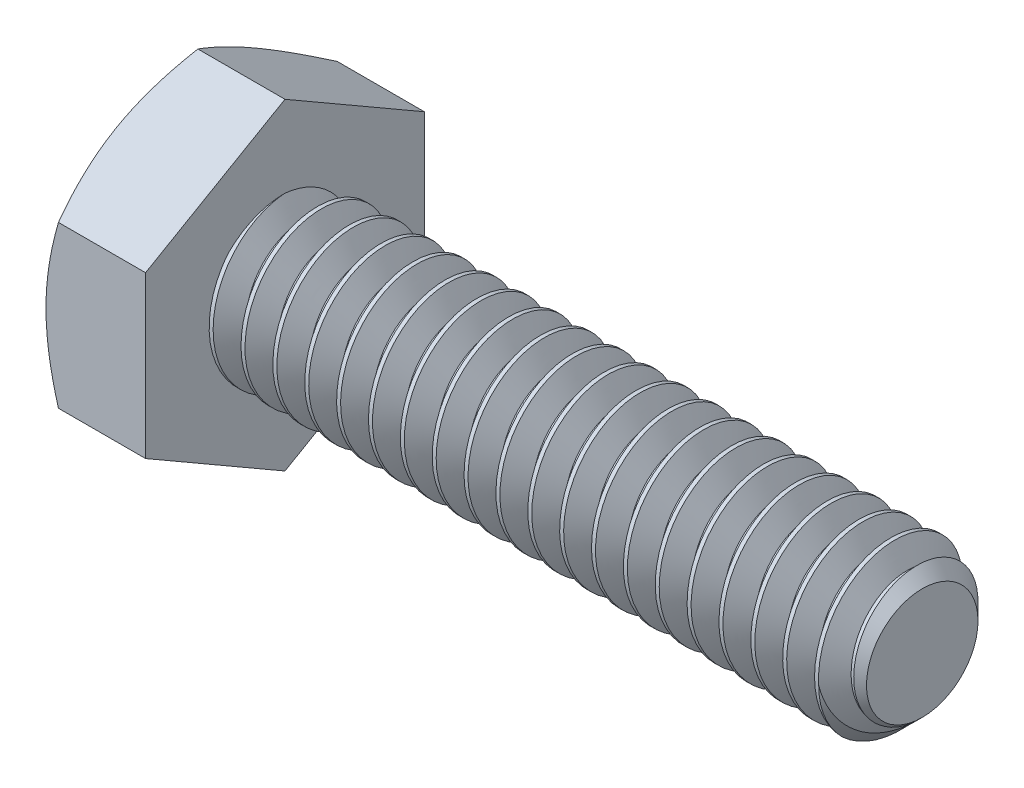
SolidWorks part; units mm, degrees
ref_plane "Front Plane" through (0, 0, 0) normal (0, 0, 1) x (1, 0, 0)
ref_plane "Top Plane" through (0, 0, 0) normal (0, 1, 0) x (1, 0, 0)
ref_plane "Right Plane" through (0, 0, 0) normal (1, 0, 0) x (0, 0, -1)
sketch "Sketch1" plane through (0, 0, 0) normal (0, 0, 1) x (1, 0, 0)
  line L0 (-14.6844, 0) -> (14.6844, 0) construction
  line L1 (14.6844, 3.175) -> (14.6844, -3.175) construction
  line L2 (-10.7156, 5.5562) -> (-10.7156, -5.5562) construction
  line L3 (-14.6844, 5.5562) -> (-14.6844, -5.5562) construction
  point P9 (-10.7156, 0)
  point P10 (10.2394, -3.175)
  dimension "Screw Dia" = 6.35
  dimension "Hex" = 11.1125
  dimension "Head Ht" = 3.9688
  dimension "Screw Lenght" = 25.4
  dimension "D1" = 4.445
ref_plane "Plane2" through (14.6844, 0, 0) normal (1, 0, 0) x (0, 0, -1)
sketch "Sketch5" plane through (14.6844, 0, 0) normal (1, 0, 0) x (0, 0, -1)
  circle A0 centre (0, 0) radius 3.175
extrude "Boss-Extrude3" add sketch "Sketch5" against normal up to vertex (25.4 mm away) up to point (-10.7156, 0, 0)
sketch "Sketch9" plane through (14.6844, 0, 0) normal (1, 0, 0) x (0, 0, -1)
  circle A1 centre (0, 0) radius 3.175
  circle A2 centre (0, 0) radius 3.175
  dimension "D1" = 0
curve "Helix/Spiral1" pitch 1.27 height 26.67 turns 21 parameters "Pitch"=1.27
chamfer "Chamfer1" distance 0.9525 angle 45 1 edges at (14.6844, 0, -3.175)
sketch "Sketch10" plane through (0, 0, 0) normal (0, 0, 1) x (1, 0, 0)
  line L0 (14.6844, 3.175) -> (15.1606, 2.3501)
  line L1 (15.1606, 2.3501) -> (15.3194, 2.3501)
  line L2 (15.3194, 2.3501) -> (15.7956, 3.175)
  line L3 (14.6844, 3.175) -> (15.7956, 3.175)
  line L4 (15.24, 3.175) -> (15.24, 2.3501) construction
  line L5 (14.9225, 2.7626) -> (15.5575, 2.7626) construction
  dimension "D1" = 60
  dimension "D2" = 0.1588
  dimension "D3" = 0.635
sweep "Cut-Sweep1" cut profiles "Sketch10" path "Helix/Spiral1" align with end faces yes
sketch "Sketch6" plane through (-10.7156, 0, 0) normal (-1, 0, 0) x (0, 0, 1)
  line L0 (0, 5.5562) -> (0, -5.5562) construction
  line L1 (5.5562, 3.2079) -> (0, 6.4158)
  line L2 (0, 6.4158) -> (-5.5562, 3.2079)
  line L3 (-5.5562, 3.2079) -> (-5.5562, -3.2079)
  line L4 (-5.5562, -3.2079) -> (0, -6.4158)
  line L5 (0, -6.4158) -> (5.5563, -3.2079)
  line L6 (5.5563, -3.2079) -> (5.5562, 3.2079)
  circle A0 centre (0, 0) radius 5.5562 construction
extrude "Boss-Extrude4" add sketch "Sketch6" along normal up to vertex (3.9688 mm away) up to point (-14.6844, -5.5562, 0)
sketch "Sketch7" plane through (-14.6844, 0, 0) normal (-1, 0, 0) x (0, 0, 1)
  circle A0 centre (0, 0) radius 5.5562 construction
  circle A1 centre (0, 0) radius 5.5562
sketch "Sketch8" plane through (-14.6844, 0, 0) normal (-1, 0, 0) x (0, 0, 1)
  circle A0 centre (0, 0) radius 5.5562 construction
  circle A1 centre (0, 0) radius 5.5562
extrude "Cut-Extrude3" cut sketch "Sketch8" against normal through all draft 60 flip side to cut
equation "\"D2@Sketch10\" = \"Pitch@Helix/Spiral1\"*.125"
equation "\"D3@Sketch10\" = \"Pitch@Helix/Spiral1\"*.5"
equation "\"D3@Helix/Spiral1\" = \"Screw Lenght@Sketch1\"+\"Pitch@Helix/Spiral1\""
equation "\"D1@Chamfer1\" = \"Pitch@Helix/Spiral1\"*.75"
equation "\"D1@Sketch1\" = \"Pitch@Helix/Spiral1\"*3.5"
